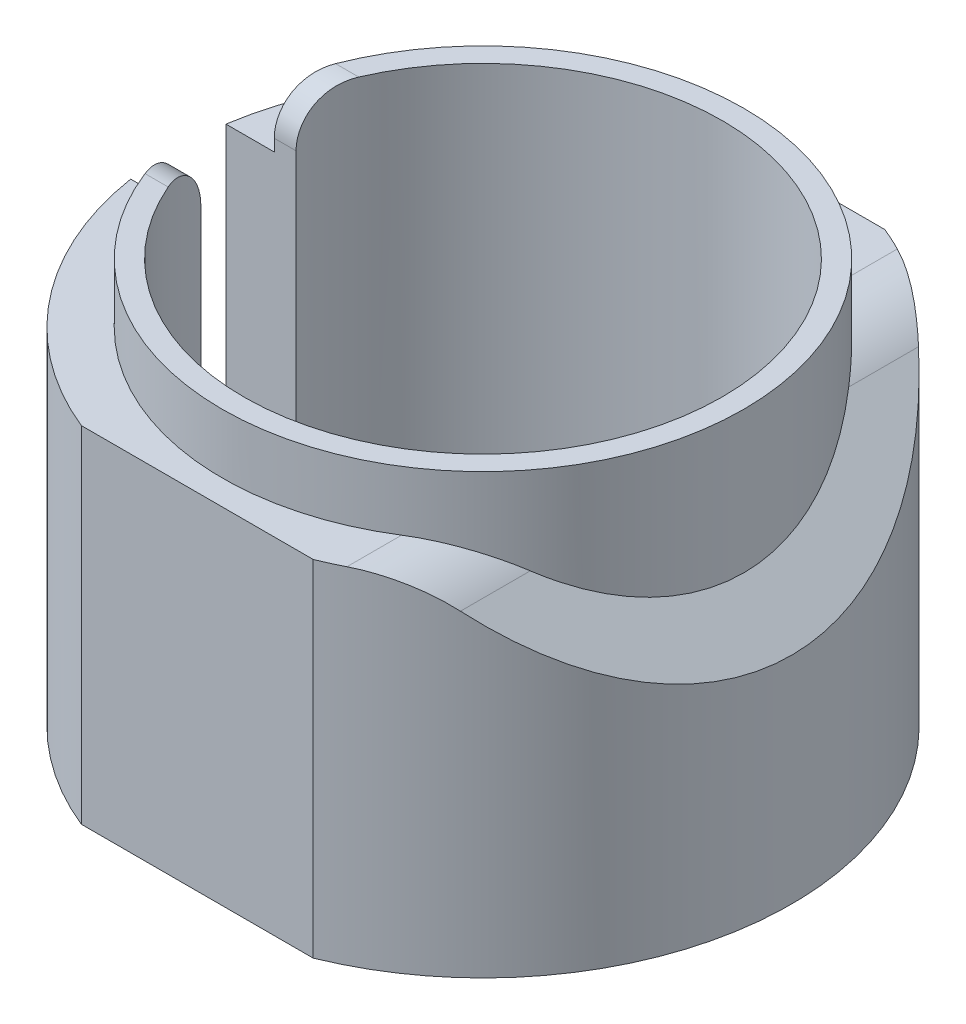
SolidWorks part; units mm, degrees
ref_plane "Front Plane" through (0, 0, 0) normal (0, 0, 1) x (1, 0, 0)
ref_plane "Top Plane" through (0, 0, 0) normal (0, 1, 0) x (1, 0, 0)
ref_plane "Right Plane" through (0, 0, 0) normal (1, 0, 0) x (0, 0, -1)
sketch "Sketch1" plane through (0, 0, 0) normal (0, 1, 0) x (1, 0, 0)
  circle A0 centre (0, 0) radius 10.05
  circle A1 centre (0, 0) radius 10.95
  dimension "D1" = 20.1
  dimension "D2" = 21.9
extrude "Boss-Extrude1" add sketch "Sketch1" against normal blind 2 contours A1 A0 | A0 | A0 | A1 region at (0, 0, 0) region at (-10.6403, 0, 0)
extrude "Boss-Extrude2" add sketch "Sketch1<3>" along normal blind 15
sketch "Sketch1<3>" plane through (0, 0, 0) normal (0, 1, 0) x (1, 0, 0) same geometry as "Sketch1"
sketch "Sketch2" plane through (0, 15, 0) normal (0, 1, 0) x (1, 0, 0)
  circle A0 centre (0, 0) radius 10.95
  circle A1 centre (0, 0) radius 12.95
  circle A2 centre (0, 0) radius 10.95 construction
  dimension "D1" = 2
extrude "Boss-Extrude3" add sketch "Sketch2" against normal up to surface (17 mm away) from offset 2.5 up to face at (0, -2, 10.95) offset against normal yes
sketch "Sketch3" plane through (0, 0, 0) normal (0, 1, 0) x (1, 0, 0)
  line L0 (-50, 12) -> (-50, 36)
  line L1 (-50, -12) -> (50, -12)
  line L2 (-50, -12) -> (-50, 12)
  line L3 (-50, 12) -> (50, 12)
  line L4 (50, -12) -> (50, 12)
  line L5 (-50, -12) -> (50, 12) construction
  line L6 (-50, 12) -> (50, -12) construction
  line L7 (-50, 12) -> (50, 12)
  line L8 (-50, 36) -> (50, 36)
  line L9 (50, 12) -> (50, 36)
  line L10 (50, -12) -> (-50, -12)
  line L11 (50, -12) -> (50, -36)
  line L12 (-50, -12) -> (-50, -36)
  line L13 (50, -36) -> (-50, -36)
  point P0 (0, 0)
  point P6 (0, 0)
  dimension "D1" = 24
  dimension "D2" = 100
extrude "Cut-Extrude1" cut sketch "Sketch3" against normal through all both and the other way through all contours L13 L11 L1 L12 | L3 L9 L8 L0 | L0 L7 L9 L8 region at (0, 0, -24) region at (0, 0, 24)
sketch "Sketch4" plane through (0, 0, 0) normal (0, 0, 1) x (1, 0, 0)
  line L0 (5, 15) -> (13, 7)
  line L1 (0, 0) -> (13, 0)
  line L2 (0, 0) -> (0, 15)
  line L3 (0, 15) -> (13, 15)
  line L4 (13, 0) -> (13, 15)
  line L5 (13, 7) -> (5, 7)
  line L6 (13, 7) -> (13, 15)
  line L7 (13, 15) -> (5, 15)
  line L8 (5, 7) -> (5, 15)
  dimension "D1" = 13
  dimension "D2" = 15
  dimension "D3" = 5
extrude "Cut-Extrude3" cut sketch "Sketch4" against normal through all both and the other way through all contours L0 L4 L3 region at (10.3333, 12.3333, 0)
extrude "Boss-Extrude4" add sketch "Sketch1<4>" along normal blind 15
sketch "Sketch1<4>" plane through (0, 0, 0) normal (0, 1, 0) x (1, 0, 0) same geometry as "Sketch1"
sketch "Sketch5" plane through (0, 0, 0) normal (0, 1, 0) x (1, 0, 0)
  line L0 (-2, -2) -> (-2, 2)
  line L1 (2, 2) -> (-2, 2)
  line L2 (2, 2) -> (2, -2)
  line L3 (2, -2) -> (-2, -2)
  line L4 (-2, 2) -> (-2, -2)
  line L5 (2, 2) -> (-2, -2) construction
  line L6 (2, -2) -> (-2, 2) construction
  line L7 (-2, -2) -> (-20, -2)
  line L8 (-2, 2) -> (-20, 2)
  line L9 (-20, -2) -> (-20, 2)
  point P0 (0, 0)
  dimension "D1" = 4
  dimension "D2" = 20
extrude "Cut-Extrude4" cut sketch "Sketch5" along normal through all contours L9 L7 L0 L8 region at (-11, 0, 0)
fillet "Fillet1" radius 2 4 edges at (-10.3074, 15, 2) (-10.3074, 15, -2) (-11.3218, 0, -2) (-11.3218, 0, 2)
fillet "Fillet2" radius 4 2 edges at (7.5, 12.5, 9.2677) (7.5, 12.5, -9.2677)
sketch "Sketch6" plane through (0, 0, 0) normal (0, 1, 0) x (1, 0, 0)
  circle A0 centre (0, 0) radius 1.6
  dimension "D1" = 3.2
extrude "Cut-Extrude5" cut sketch "Sketch6" against normal through all both and the other way through all
